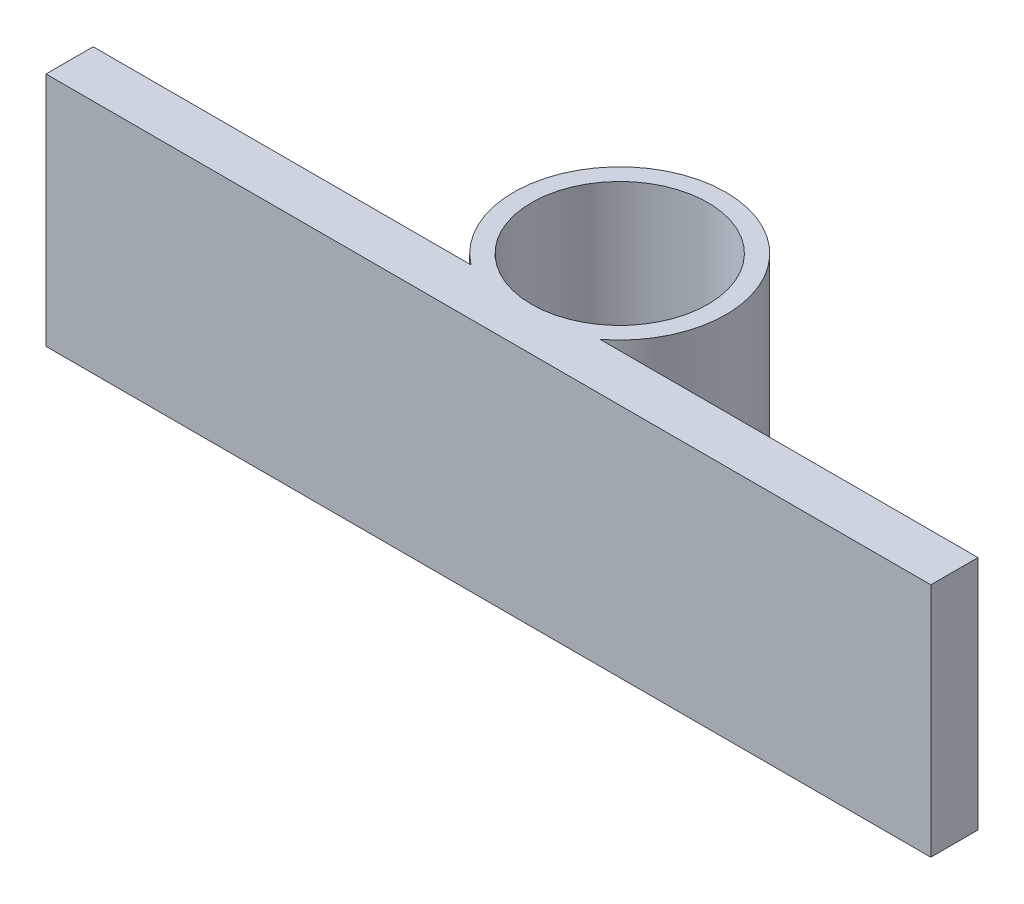
SolidWorks part; units mm, degrees
ref_plane "Front Plane" through (0, 0, 0) normal (0, 0, 1) x (1, 0, 0)
ref_plane "Top Plane" through (0, 0, 0) normal (0, 1, 0) x (1, 0, 0)
ref_plane "Right Plane" through (0, 0, 0) normal (1, 0, 0) x (0, 0, -1)
sketch "Sketch1" plane through (0, 0, 0) normal (0, 0, 1) x (1, 0, 0)
  line L1 (-94.1406, 21.747) -> (96.3594, 21.747)
  line L2 (-94.1406, 21.747) -> (-94.1406, -29.053)
  line L3 (-94.1406, -29.053) -> (96.3594, -29.053)
  line L4 (96.3594, 21.747) -> (96.3594, -29.053)
  dimension "D1" = 190.5
  dimension "D2" = 50.8
extrude "Boss-Extrude1" add sketch "Sketch1" along normal blind 10.16
sketch "Sketch5" plane through (0, 21.747, 0) normal (0, 1, 0) x (1, 0, 0)
  line L0 (7.7134, 0) -> (7.7134, -10.16)
  line L1 (96.3594, 0) -> (-94.1406, 0) construction
  line L2 (96.3594, -10.16) -> (-94.1406, -10.16) construction
  line L3 (-5.4946, 0) -> (-5.4946, -10.16)
  point P8 (1.1094, 0)
  dimension "D1" = 6.604
  dimension "D2" = 6.604
sketch "Sketch6" plane through (0, 21.747, 0) normal (0, 1, 0) x (1, 0, 0)
  arc A0 (7.7134, 0) -> (-5.4946, 0) centre (1.1094, 10.8827) cw
extrude "Cut-Extrude1" cut sketch "Sketch6" against normal through all and the other way through all flip side to cut
sketch "Sketch7" plane through (0, 21.747, 0) normal (0, 1, 0) x (1, 0, 0)
  line L0 (1.0861, -4.7215) -> (1.0874, 18.1385)
  circle A1 centre (1.0874, 18.1385) radius 22.8473
  point P2 (1.1057, 18.2674)
  point P3 (1.0861, 18.1385)
  point P7 (1.1094, 21.013)
  point P8 (1.1094, 21.013)
  dimension "D1" = 22.86
extrude "Boss-Extrude2" add sketch "Sketch7" against normal through all contours A1
sketch "Sketch8" plane through (0, 21.747, 0) normal (0, 1, 0) x (1, 0, 0)
  circle A0 centre (1.0874, 18.1385) radius 18.9865
  point P3 (1.1094, 21.013)
  point P4 (1.0035, 18.1145)
  point P5 (1.0874, 14.3285)
  point P6 (1.0874, 18.1385)
  point P7 (1.1457, 17.2357)
  dimension "D1" = 37.973
extrude "Cut-Extrude2" cut sketch "Sketch8" against normal blind 48.26
sketch "Sketch9" plane through (0, -26.513, 0) normal (0, 1, 0) x (1, 0, 0)
  circle A0 centre (1.0874, 18.1385) radius 7.9375
  circle A1 centre (1.0874, 18.1385) radius 18.9865 construction
  point P2 (1.7521, 17.5094)
  point P4 (0, 15.592)
  point P5 (0.6404, 15.3132)
  point P6 (0.966, 16.6898)
  point P7 (0, 17.566)
  dimension "D1" = 15.875
  dimension "D2" = 0
extrude "Cut-Extrude3" cut sketch "Sketch9" against normal through all
